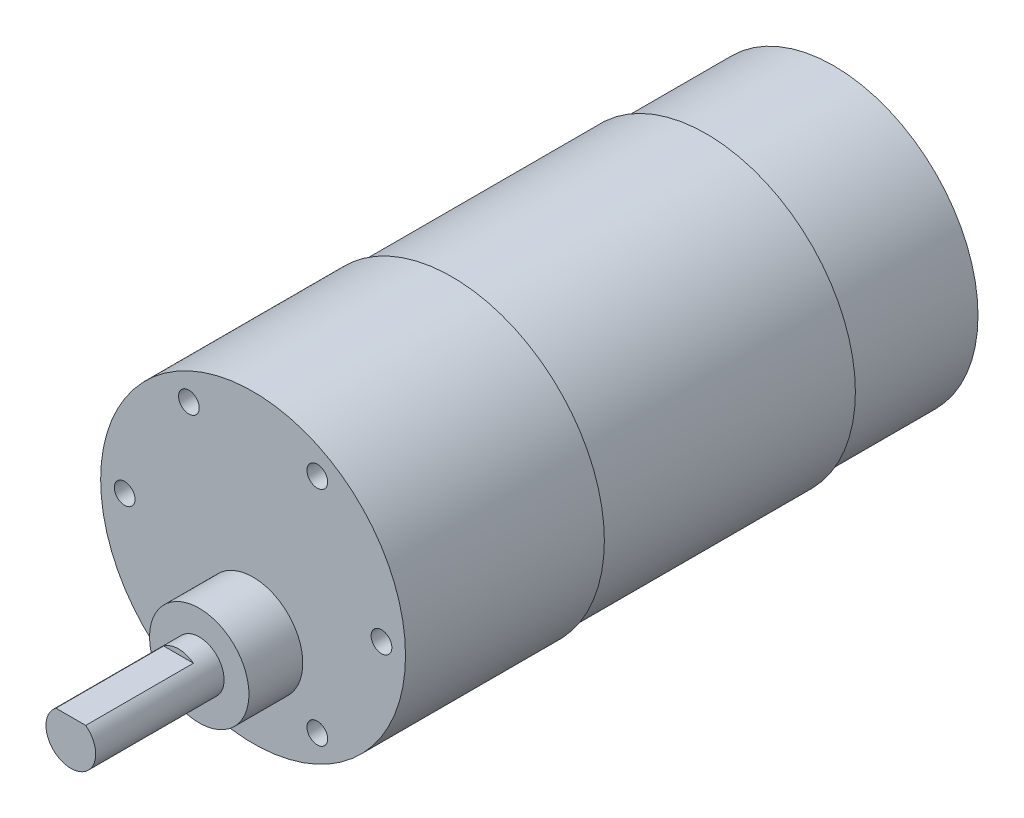
SolidWorks part; units mm, degrees
ref_plane "Front Plane" through (0, 0, 0) normal (0, 0, 1) x (1, 0, 0)
ref_plane "Top Plane" through (0, 0, 0) normal (0, 1, 0) x (1, 0, 0)
ref_plane "Right Plane" through (0, 0, 0) normal (1, 0, 0) x (0, 0, -1)
sketch "Sketch1" plane through (0, 0, 0) normal (0, 0, 1) x (1, 0, 0)
  circle A0 centre (0, 0) radius 17.4
  dimension "D1" = 34.8
extrude "Boss-Extrude1" add sketch "Sketch1" along normal blind 15.4
sketch "Sketch2" plane through (0, 0, 15.4) normal (0, 0, 1) x (1, 0, 0)
  circle A0 centre (0, 0) radius 18
  dimension "D1" = 36
extrude "Boss-Extrude2" add sketch "Sketch2" along normal blind 30.7
sketch "Sketch3" plane through (0, 0, 46.1) normal (0, 0, 1) x (1, 0, 0)
  circle A0 centre (0, 0) radius 18.4
  dimension "D1" = 36.8
extrude "Boss-Extrude3" add sketch "Sketch3" along normal blind 24
sketch "Sketch4" plane through (0, 0, 70.1) normal (0, 0, 1) x (1, 0, 0)
  circle A0 centre (0, -7) radius 6
  dimension "D2" = 12
  dimension "D1" = 7
extrude "Boss-Extrude4" add sketch "Sketch4" along normal blind 6.5
sketch "Sketch5" plane through (0, 0, 76.6) normal (0, 0, 1) x (1, 0, 0)
  circle A0 centre (0, -7) radius 3
  dimension "D1" = 6
extrude "Boss-Extrude5" add sketch "Sketch5" along normal blind 15.5
sketch "Sketch6" plane through (0, 0, 92.1) normal (0, 0, 1) x (1, 0, 0)
  line L0 (-1.8, -4.6) -> (1.8, -4.6)
  circle A0 centre (0, -7) radius 3 construction
  circle A1 centre (0, -7) radius 3 construction
  arc A2 (-1.8, -4.6) -> (1.8, -4.6) centre (0, -7) cw
  dimension "D1" = 2.4
extrude "Cut-Extrude1" cut sketch "Sketch6" against normal blind 13
hole_wizard "Tap Drill for M3x0.5 Tap1" positions "Sketch7" profile "Sketch8" hole size "M3x0.5" standard "ANSI Metric"
sketch "Sketch7" plane through (0, 0, 70.1) normal (0, 0, 1) x (1, 0, 0)
  circle A0 centre (0, 0) radius 15.5
  point P0 (-15.5, 0)
  point P13 (-7.75, 13.4234)
  point P14 (7.75, 13.4234)
  point P15 (15.5, 0)
  point P16 (7.75, -13.4234)
  point P17 (-7.75, -13.4234)
  dimension "D1" = 15.5
  dimension "D2" = 6
sketch "Sketch8" plane through (-15.5, 0, 70.1) normal (1, 0, 0) x (0, -1, 0)
  line L0 (0, 0) -> (0, 10.76)
  line L1 (0, 10.76) -> (1.25, 10.76)
  line L2 (1.25, 10.76) -> (1.25, 0)
  line L5 (1.25, 0) -> (0, 0)
  line L10 (0, 10.76) -> (-1.25, 10.76) construction
  line L11 (0, -6.35) -> (0, 107.95) construction
  dimension "Hole Dia." = 2.5
  dimension "Hole Depth" = 10.76
  dimension "Drill Angle" = 180
